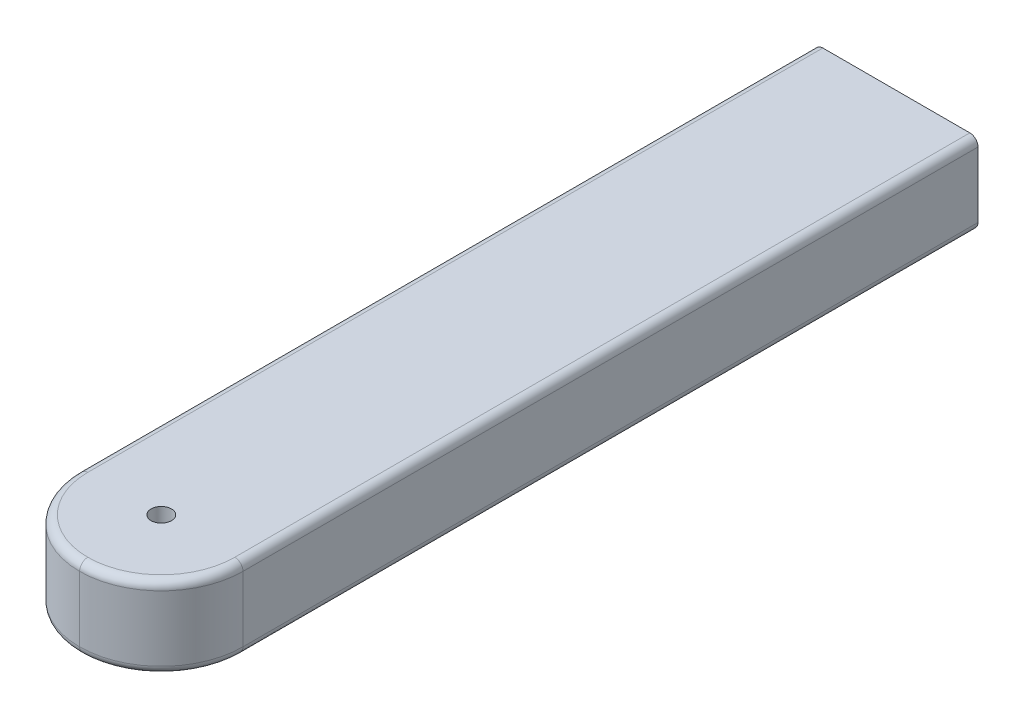
SolidWorks part; units mm, degrees
material "Oak"
ref_plane "Front" through (0, 0, 0) normal (0, 0, 1) x (1, 0, 0)
ref_plane "Top" through (0, 0, 0) normal (0, 1, 0) x (1, 0, 0)
ref_plane "Right" through (0, 0, 0) normal (1, 0, 0) x (0, 0, -1)
sketch "Sketch1" plane through (0, 0, 0) normal (0, 0, 1) x (1, 0, 0)
  line L1 (0, 0) -> (-50.8, 0)
  line L2 (0, 0) -> (0, 25.4)
  line L3 (0, 25.4) -> (-50.8, 25.4)
  line L4 (-50.8, 0) -> (-50.8, 25.4)
  dimension "D1" = 50.8
  dimension "D2" = 25.4
extrude "Boss-Extrude1" add sketch "Sketch1" along normal blind 254
sketch "Sketch2" plane through (0, 0, 0) normal (0, 0, -1) x (-1, 0, 0)
  line L0 (50.8, 12.7) -> (0, 12.7) construction
  line L1 (50.8, 25.4) -> (50.8, 0) construction
  line L2 (0, 0) -> (0, 25.4) construction
  circle A0 centre (25.4, 12.7) radius 3.175
  dimension "D1" = 6.35
extrude "Cut-Extrude1" cut sketch "Sketch2" against normal blind 25.4
fillet "Fillet2" radius 25.4 2 edges at (0, 12.7, 254) (-50.8, 12.7, 254)
fillet "Fillet1" radius 2.54 8 edges at (-50.8, 25.4, 114.3) (0, 25.4, 114.3) (0, 0, 114.3) (-50.8, 0, 114.3) (-43.3605, 25.4, 246.5605) (-7.4395, 25.4, 246.5605) (-7.4395, 0, 246.5605) (-43.3605, 0, 246.5605)
sketch "Sketch3" plane through (0, 25.4, 0) normal (0, 1, 0) x (1, 0, 0)
  circle A0 centre (-25.4, -228.6) radius 3.175
  arc A2 (-48.26, -228.6) -> (-25.4, -251.46) centre (-25.4, -228.6) ccw construction
  dimension "D1" = 6.35
extrude "Cut-Extrude2" cut sketch "Sketch3" against normal through all and the other way through all
